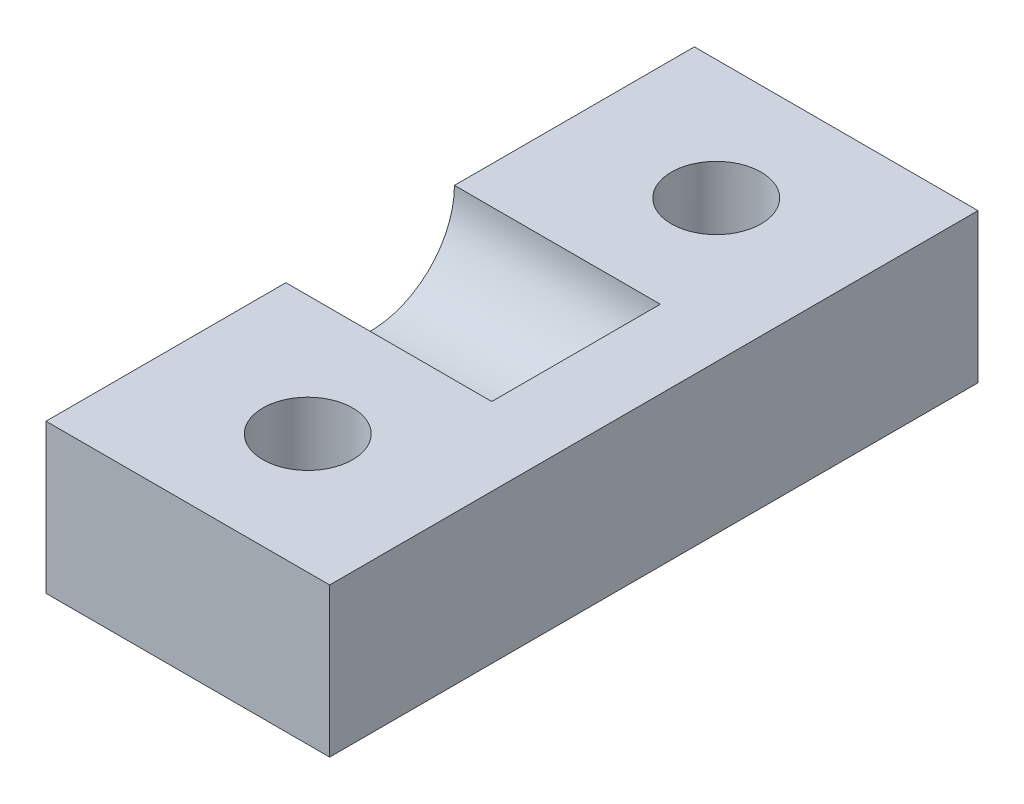
SolidWorks part; units mm, degrees
ref_plane "Front Plane" through (0, 0, 0) normal (0, 0, 1) x (1, 0, 0)
ref_plane "Top Plane" through (0, 0, 0) normal (0, 1, 0) x (1, 0, 0)
ref_plane "Right Plane" through (0, 0, 0) normal (1, 0, 0) x (0, 0, -1)
sketch "Sketch1" plane through (0, 0, 0) normal (0, 1, 0) x (1, 0, 0)
  line L1 (-5.5563, -12.7) -> (5.5562, -12.7)
  line L2 (-5.5563, -12.7) -> (-5.5563, 12.7)
  line L3 (-5.5563, 12.7) -> (5.5562, 12.7)
  line L4 (5.5562, -12.7) -> (5.5562, 12.7)
  line L5 (-5.5563, -12.7) -> (5.5562, 12.7) construction
  line L6 (-5.5563, 12.7) -> (5.5562, -12.7) construction
  point P0 (0, 0)
  dimension "D1" = 11.1125
  dimension "D2" = 25.4
extrude "Boss-Extrude1" add sketch "Sketch1" against normal blind 6.35
sketch "Sketch2" plane through (-5.5563, 0, 0) normal (-1, 0, 0) x (0, 0, 1)
  circle A0 centre (0, 0) radius 3.302
  dimension "D1" = 6.604
extrude "Cut-Extrude1" cut sketch "Sketch2" against normal blind 8.0645
sketch "Sketch3" plane through (0, 0, 0) normal (0, 1, 0) x (1, 0, 0)
  line L1 (0, -12.7) -> (0, 12.7) construction
  line L3 (-5.5563, -12.7) -> (5.5562, -12.7) construction
  line L4 (5.5562, 12.7) -> (-5.5563, 12.7) construction
  line L5 (-5.5562, -8.001) -> (5.5562, -8.001) construction
  line L6 (-5.5563, -3.302) -> (-5.5563, -12.7) construction
  line L7 (5.5562, -12.7) -> (5.5562, 12.7) construction
  line L8 (-5.5562, 8.001) -> (5.5562, 8.001) construction
  line L9 (-5.5563, 12.7) -> (-5.5563, 3.302) construction
  circle A0 centre (0, 8.001) radius 1.759
  circle A1 centre (0, -8.001) radius 1.759
  dimension "D2" = 3.5179
extrude "Cut-Extrude2" cut sketch "Sketch3" against normal up to next
chamfer "Chamfer1" distance 0.508 angle 45 4 edges at (0, -6.35, 12.7) (-5.5563, -6.35, 0) (0, -6.35, -12.7) (5.5562, -6.35, 0)
